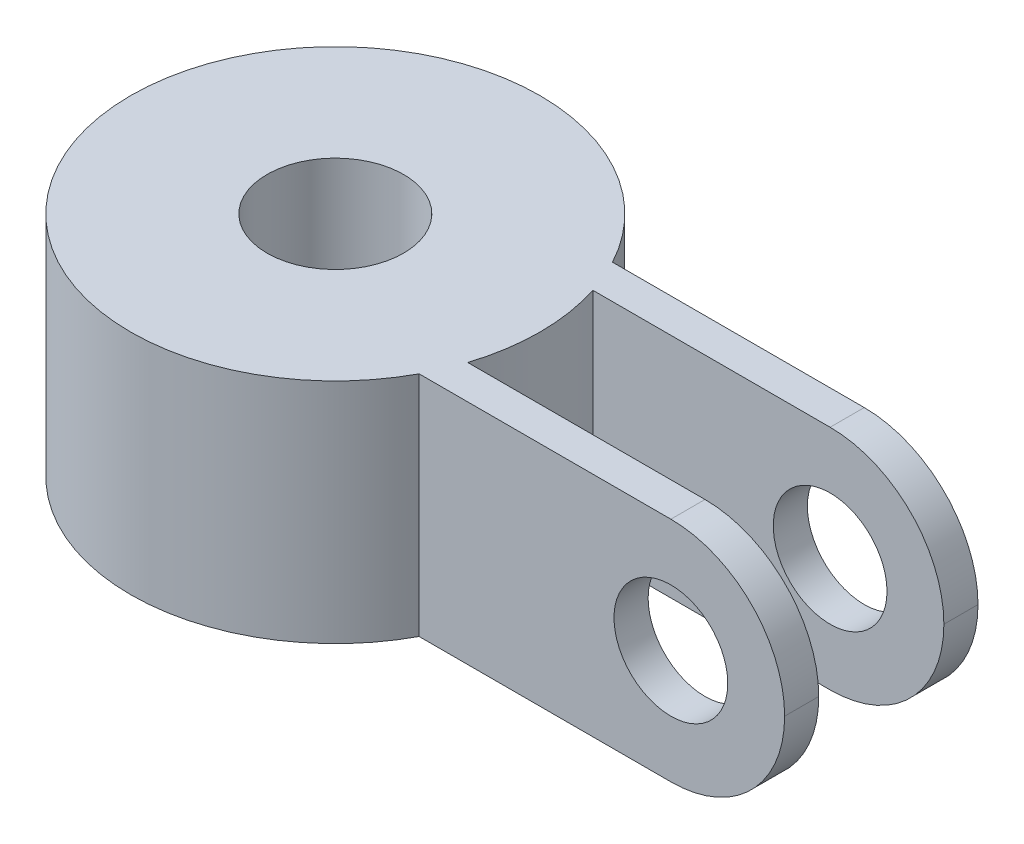
SolidWorks part; units mm, degrees
ref_plane "Front Plane" through (0, 0, 0) normal (0, 0, 1) x (1, 0, 0)
ref_plane "Top Plane" through (0, 0, 0) normal (0, 1, 0) x (1, 0, 0)
ref_plane "Right Plane" through (0, 0, 0) normal (1, 0, 0) x (0, 0, -1)
sketch "Sketch1" plane through (0, 0, 0) normal (0, 1, 0) x (1, 0, 0)
  circle A0 centre (0, 0) radius 9
  circle A1 centre (0, 0) radius 3
  dimension "D1" = 18
  dimension "D2" = 6
extrude "Boss-Extrude1" add sketch "Sketch1" along normal blind 10
sketch "Sketch5" plane through (0, 0, 0) normal (0, -1, 0) x (1, 0, 0)
  line L0 (7.9333, 4.25) -> (24, 4.25)
  line L1 (24, 4.25) -> (24, 2.75)
  line L2 (24, 2.75) -> (7.138, 2.75)
  line L3 (7.138, 2.75) -> (7.9333, 4.25)
  line L4 (0, 0) -> (13.2148, 0) construction
  line L5 (7.138, -2.75) -> (7.9333, -4.25)
  line L6 (7.9333, -4.25) -> (24, -4.25)
  line L7 (24, -4.25) -> (24, -2.75)
  line L8 (24, -2.75) -> (7.138, -2.75)
  circle A0 centre (0, 0) radius 9 construction
  dimension "D1" = 33
  dimension "D2" = 1.5
  dimension "D3" = 5.5
extrude "Boss-Extrude3" add sketch "Sketch5" against normal up to surface (10 mm away) up to face at (0, 10, 9)
fillet "Fillet1" radius 5 4 edges at (24, 0, -3.5) (24, 10, -3.5) (24, 10, 3.5) (24, 0, 3.5)
sketch "Sketch6" plane through (0, 0, 4.25) normal (0, 0, 1) x (1, 0, 0)
  circle A0 centre (19, 5) radius 2.5
  arc A1 (24, 5) -> (19, 10) centre (19, 5) ccw construction
  dimension "D1" = 5
extrude "Cut-Extrude2" cut sketch "Sketch6" against normal blind 25
